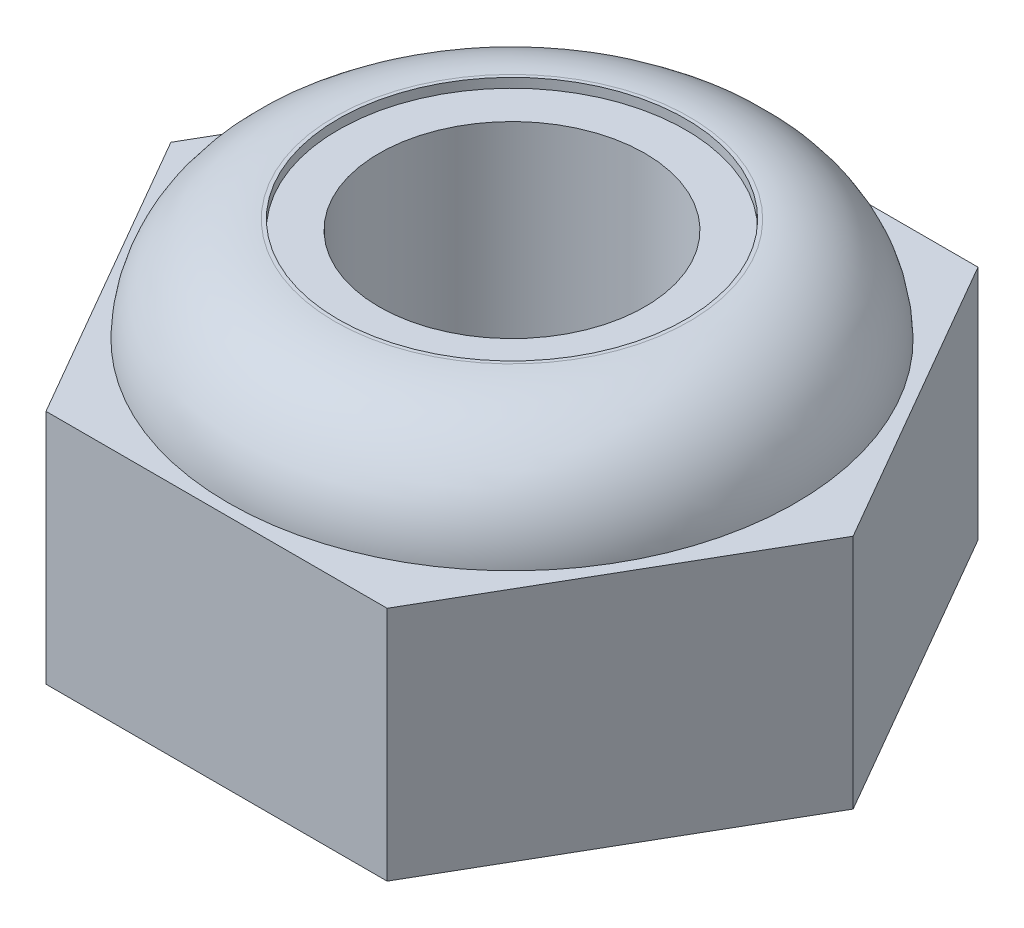
SolidWorks part; units mm, degrees
ref_plane "Front Plane" through (0, 0, 0) normal (0, 0, 1) x (1, 0, 0)
ref_plane "Top Plane" through (0, 0, 0) normal (0, 1, 0) x (1, 0, 0)
ref_plane "Right Plane" through (0, 0, 0) normal (1, 0, 0) x (0, 0, -1)
sketch "Sketch1" plane through (0, 0, 0) normal (0, 1, 0) x (1, 0, 0)
  line L1 (3.6662, 0) -> (1.8331, 3.175)
  line L2 (1.8331, 3.175) -> (-1.8331, 3.175)
  line L3 (-1.8331, 3.175) -> (-3.6662, 0)
  line L4 (-3.6662, 0) -> (-1.8331, -3.175)
  line L5 (-1.8331, -3.175) -> (1.8331, -3.175)
  line L6 (1.8331, -3.175) -> (3.6662, 0)
  circle A0 centre (0, 0) radius 3.175 construction
  dimension "D1" = 6.35
extrude "Boss-Extrude1" add sketch "Sketch1" along normal blind 2.54
sketch "Sketch2" plane through (0, 2.54, 0) normal (0, 1, 0) x (1, 0, 0)
  circle A0 centre (0, 0) radius 3.048
  circle A1 centre (0, 0) radius 1.8669
  dimension "D1" = 6.096
  dimension "D2" = 3.7338
extrude "Boss-Extrude2" add sketch "Sketch2" along normal offset from surface (1.1176 mm away) 3.6576 up to face at (0, 0, 0)
fillet "Fillet1" radius 1.143 1 edges at (0, 3.6576, 3.048)
sketch "Sketch3" plane through (0, 2.54, 0) normal (0, 1, 0) x (1, 0, 0)
  circle A0 centre (0, 0) radius 1.8669
  circle A1 centre (0, 0) radius 1.4287
  circle A2 centre (0, 0) radius 1.8669 construction
  dimension "D1" = 2.8575
extrude "Boss-Extrude3" add sketch "Sketch3" along normal blind 1.016
sketch "Sketch4" plane through (0, 2.54, 0) normal (0, 1, 0) x (1, 0, 0)
  circle A0 centre (0, 0) radius 1.4287
  circle A1 centre (0, 0) radius 1.4287 construction
extrude "Cut-Extrude1" cut sketch "Sketch4" against normal through all
